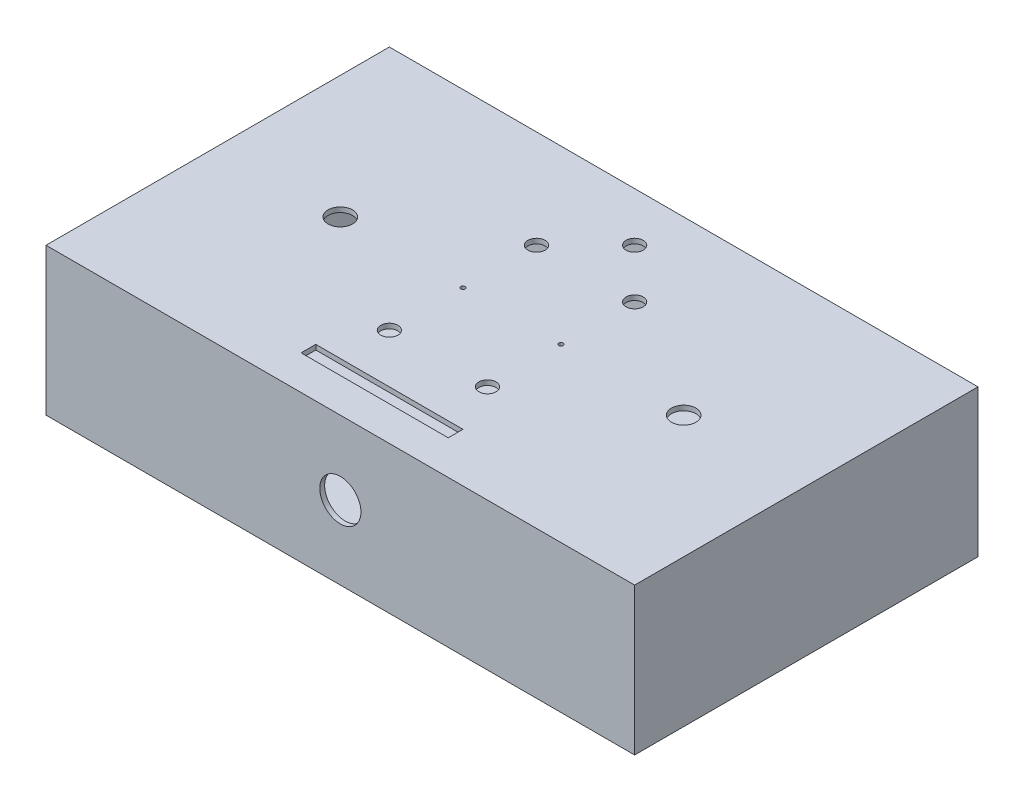
SolidWorks part; units mm, degrees
ref_plane "Front Plane" through (0, 0, 0) normal (0, 0, 1) x (1, 0, 0)
ref_plane "Top Plane" through (0, 0, 0) normal (0, 1, 0) x (1, 0, 0)
ref_plane "Right Plane" through (0, 0, 0) normal (1, 0, 0) x (0, 0, -1)
sketch "Sketch1" plane through (0, 0, 0) normal (0, 1, 0) x (1, 0, 0)
  line L1 (-152.4, 88.9) -> (152.4, 88.9)
  line L2 (-152.4, 88.9) -> (-152.4, -88.9)
  line L3 (-152.4, -88.9) -> (152.4, -88.9)
  line L4 (152.4, 88.9) -> (152.4, -88.9)
  dimension "D1" = 304.8
  dimension "D2" = 177.8
  dimension "D3" = 88.9
  dimension "D4" = 152.4
extrude "Boss-Extrude1" add sketch "Sketch1" along normal blind 76.2
shell "Shell1" thickness 2.54
sketch "Sketch3" plane through (0, 76.2, 0) normal (0, 1, 0) x (1, 0, 0)
  line L0 (0, -41.91) -> (0, 41.91) construction
  circle A0 centre (-88.9, 0) radius 6.35
  circle A1 centre (88.9, 0) radius 6.35
  dimension "D1" = 12.7
  dimension "D2" = 12.7
  dimension "D3" = 88.9
  dimension "D4" = 88.9
extrude "Cut-Extrude1" cut sketch "Sketch3" against normal blind 2.54
hole_wizard "#4-40 Tapped Hole1" positions "Sketch9" profile "Sketch8" tap size "#4-40" standard "ANSI Inch" end condition up to next
sketch "Sketch9" plane through (0, 76.2, 0) normal (0, 1, 0) x (1, 0, 0)
  line L0 (0, -41.91) -> (0, 41.91) construction
  point P0 (-25.4, 0)
  point P2 (25.4, 0)
  dimension "D1" = 25.4
  dimension "D2" = 25.4
sketch "Sketch8" plane through (-25.4, 76.2, 0) normal (1, 0, 0) x (0, 0, 1)
  line L0 (0, 0) -> (0, 2.54)
  line L1 (0, 2.54) -> (1.1303, 2.54)
  line L2 (1.1303, 2.54) -> (1.1303, 0)
  line L5 (1.1303, 0) -> (0, 0)
  line L11 (0, -6.35) -> (0, 107.95) construction
  dimension "Thread Major Dia." = 2.2606
  dimension "Thru Tap Drill Depth" = 2.54
sketch "Sketch10" plane through (0, 76.2, 0) normal (0, 1, 0) x (1, 0, 0)
  line L1 (-29.0322, 16.1544) -> (29.0322, 16.1544)
  line L2 (-29.0322, 16.1544) -> (-29.0322, -16.1544)
  line L3 (-29.0322, -16.1544) -> (29.0322, -16.1544)
  line L4 (29.0322, 16.1544) -> (29.0322, -16.1544)
  dimension "D1" = 16.1544
  dimension "D2" = 32.3088
  dimension "D3" = 29.0322
  dimension "D4" = 58.0644
sketch "Sketch11" plane through (0, 76.2, 0) normal (0, 1, 0) x (1, 0, 0)
  line L0 (0, -41.91) -> (0, 41.91) construction
  line L1 (-41.91, 0) -> (41.91, 0) construction
  circle A0 centre (-25.4, 38.1) radius 4.445
  circle A1 centre (25.4, 38.1) radius 4.445
  circle A2 centre (25.4, -38.1) radius 4.445
  circle A3 centre (-25.4, -38.1) radius 4.445
  dimension "D1" = 8.89
  dimension "D2" = 25.4
  dimension "D3" = 25.4
  dimension "D4" = 38.1
  dimension "D5" = 76.2
extrude "Cut-Extrude2" cut sketch "Sketch11" against normal blind 2.54
sketch "Sketch12" plane through (0, 76.2, 0) normal (0, 1, 0) x (1, 0, 0)
  line L0 (-41.91, 0) -> (41.91, 0) construction
  line L2 (-38.1, -63.5) -> (38.1, -63.5)
  line L3 (-38.1, -63.5) -> (-38.1, -71.12)
  line L4 (-38.1, -71.12) -> (38.1, -71.12)
  line L5 (38.1, -63.5) -> (38.1, -71.12)
  circle A0 centre (0, 63.5) radius 4.445
  dimension "D6" = 8.89
  dimension "D1" = 63.5
  dimension "D2" = 63.5
  dimension "D3" = 7.62
  dimension "D4" = 76.2
  dimension "D5" = 38.1
extrude "Cut-Extrude3" cut sketch "Sketch12" against normal blind 2.54
sketch "Sketch13" plane through (0, 0, 88.9) normal (0, 0, 1) x (1, 0, 0)
  line L0 (-152.4, 76.2) -> (-152.4, 0) construction
  circle A0 centre (0, 38.1) radius 10.6594
  point P2 (-152.4, 38.1)
  dimension "D1" = 0
extrude "Cut-Extrude4" cut sketch "Sketch13" against normal blind 2.54
